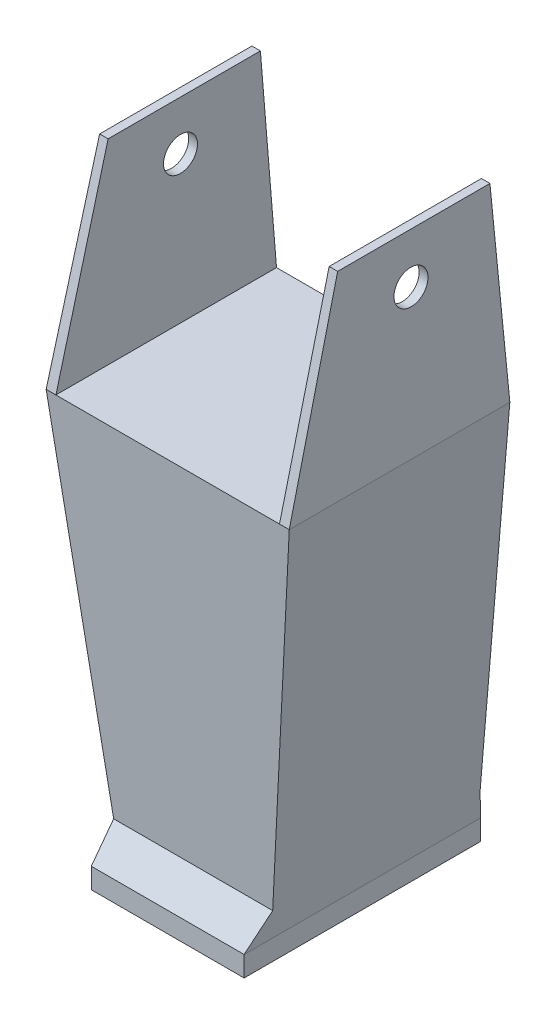
SolidWorks part; units mm, degrees
ref_plane "Front Plane" through (0, 0, 0) normal (0, 0, 1) x (1, 0, 0)
ref_plane "Top Plane" through (0, 0, 0) normal (0, 1, 0) x (1, 0, 0)
ref_plane "Right Plane" through (0, 0, 0) normal (1, 0, 0) x (0, 0, -1)
sketch "Sketch2" plane through (0, 0, 0) normal (1, 0, 0) x (0, 0, -1)
  line L0 (-35.2512, -109.956) -> (34.3588, -109.956)
  line L1 (34.3588, -109.956) -> (33.3163, -102.064)
  line L2 (33.3163, -102.064) -> (29.6988, 5.0049)
  line L3 (29.6988, 5.0049) -> (24.5837, 63.0049)
  line L4 (24.5837, 63.0049) -> (-20.2563, 63.0049)
  line L5 (-20.2563, 63.0049) -> (-35.2512, 5.0049)
  line L6 (-35.2512, 5.0049) -> (-27.7537, -102.064)
  line L7 (-27.7537, -102.064) -> (-35.2512, -109.956)
  dimension "D1" = 69.61
  dimension "D2" = 44.84
  dimension "D3" = 64.95
  dimension "D4" = 61.07
  dimension "D5" = 58
extrude "Boss-Extrude1" add sketch "Sketch2" along normal blind 71.58
sketch "Sketch4" plane through (0, 0, 0) normal (0, 0, 1) x (1, 0, 0)
  line L1 (71.58, -109.956) -> (0, -109.956) construction
  line L2 (58.29, -109.956) -> (71.58, 5.0049)
  line L7 (0, 63.0049) -> (0, 5.0049) construction
  line L8 (71.58, 5.0049) -> (0, 5.0049) construction
  line L9 (0, 5.0049) -> (13.29, -109.956)
  line L16 (0, 5.0049) -> (0, -109.956)
  line L17 (0, -109.956) -> (13.29, -109.956)
  line L18 (58.29, -109.956) -> (71.58, -109.956)
  line L19 (71.58, -109.956) -> (71.58, 5.0049)
extrude "Cut-Extrude2" cut sketch "Sketch4" against normal through all and the other way through all
sketch "Sketch5" plane through (0, 0, 0) normal (0, 0, 1) x (1, 0, 0)
  line L1 (0, 5.0049) -> (0, 63.0049)
  line L2 (0, 63.0049) -> (0.75, 63.0049)
  line L3 (71.58, 63.0049) -> (0, 63.0049) construction
  line L4 (0.75, 63.0049) -> (0, 5.0049)
  line L5 (71.58, 63.0049) -> (70.83, 63.0049)
  line L6 (70.83, 63.0049) -> (71.58, 5.0049)
  line L7 (71.58, 5.0049) -> (71.58, 63.0049)
  dimension "D1" = 0.75
  dimension "D2" = 0.75
extrude "Cut-Extrude3" cut sketch "Sketch5" against normal through all and the other way through all
sketch "Sketch9" plane through (0, 0, 0) normal (0, 0, 1) x (1, 0, 0)
  line L0 (0.375, 34.0049) -> (71.205, 34.0049) construction
  line L1 (3.25, 63.0049) -> (68.33, 63.0049)
  line L2 (3.25, 63.0049) -> (2.875, 5.0049)
  line L3 (2.875, 5.0049) -> (68.705, 5.0049)
  line L4 (68.33, 63.0049) -> (68.705, 5.0049)
  line L5 (0.75, 63.0049) -> (0, 5.0049) construction
  line L6 (71.58, 5.0049) -> (70.83, 63.0049) construction
  line L7 (71.205, 34.0049) -> (35.79, 34.0049) construction
  line L8 (35.79, 34.0049) -> (35.79, 63.0049) construction
  line L9 (70.83, 63.0049) -> (0.75, 63.0049) construction
  line L10 (35.79, 34.0049) -> (35.79, 5.0049) construction
  dimension "D1" = 65.08
  dimension "D2" = 65.83
extrude "Cut-Extrude4" cut sketch "Sketch9" against normal through all and the other way through all
sketch "Sketch16" plane through (0, 0, 0) normal (1, 0, 0) x (0, 0, -1)
  line L0 (0.8837, 71.7124) -> (0.8837, 5.0049) construction
  line L1 (-35.2512, 5.0049) -> (29.6988, 5.0049) construction
  line L2 (25.6343, 48.4049) -> (-23.3359, 48.4049) construction
  circle A0 centre (1.1492, 48.4049) radius 5
  dimension "D1" = 14.6
  dimension "D2" = 23.7
extrude "Cut-Extrude11" cut sketch "Sketch16" along normal through all
sketch "Sketch17" plane through (0, -109.956, 0) normal (0, -1, 0) x (1, 0, 0)
  line L1 (13.29, 35.2512) -> (58.29, 35.2512)
  line L2 (13.29, 35.2512) -> (13.29, -34.3588)
  line L3 (13.29, -34.3588) -> (58.29, -34.3588)
  line L4 (58.29, 35.2512) -> (58.29, -34.3588)
extrude "Boss-Extrude2" add sketch "Sketch17" along normal blind 6
sketch "Sketch18" plane through (0, -115.956, 0) normal (0, -1, 0) x (1, 0, 0)
  line L0 (13.29, 35.2512) -> (58.29, -34.3588) construction
  circle A0 centre (35.79, 0.4462) radius 4.9
extrude "Boss-Extrude3" add sketch "Sketch18" along normal blind 10
